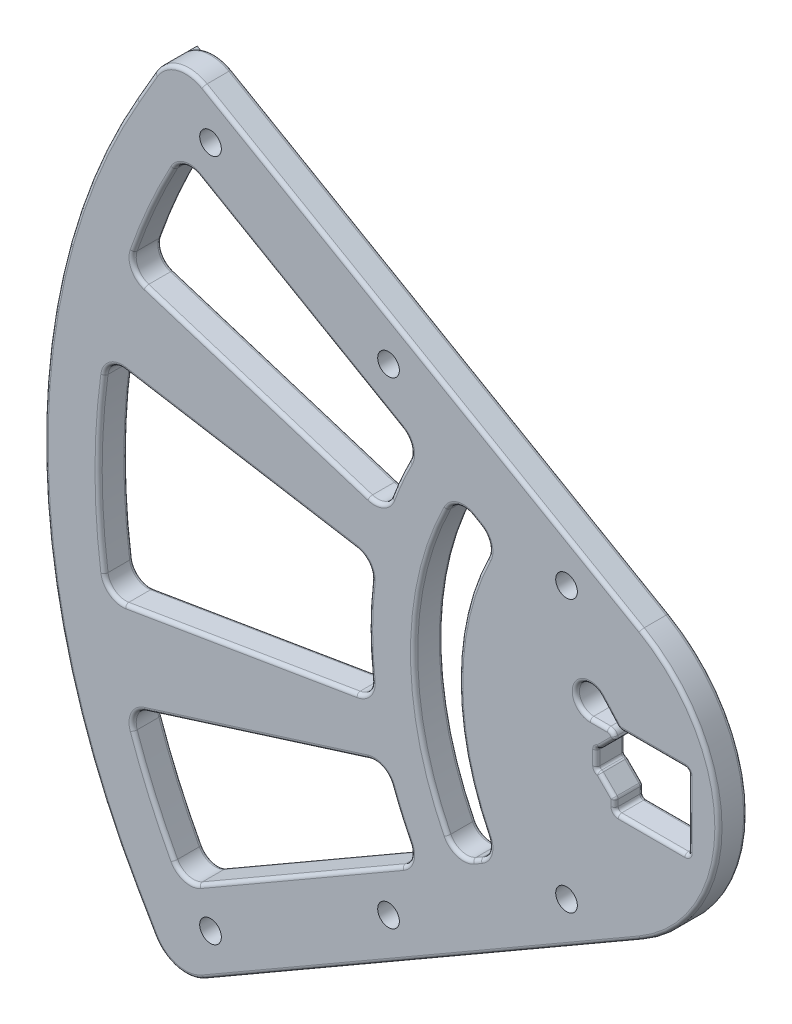
SolidWorks part; units mm, degrees
ref_plane "Front Plane" through (0, 0, 0) normal (0, 0, 1) x (1, 0, 0)
ref_plane "Top Plane" through (0, 0, 0) normal (0, 1, 0) x (1, 0, 0)
ref_plane "Right Plane" through (0, 0, 0) normal (1, 0, 0) x (0, 0, -1)
sketch "Sketch1" plane through (0, 0, 0) normal (0, 0, 1) x (1, 0, 0)
  line L0 (-3, 37.3205) -> (-366.7307, 247.3205) construction
  line L1 (-366.7307, -247.3205) -> (-3, -37.3205) construction
  line L2 (-66.0955, 46.0359) -> (-43.359, 32.909) construction
  line L3 (-66.9615, 46.5359) -> (-66.0955, 46.0359) construction
  line L4 (-66.9615, 46.5359) -> (-64.9615, 50) construction
  line L5 (-13, 20) -> (-376.7307, 230) construction
  line L6 (-43.359, -32.909) -> (-66.0955, -46.0359) construction
  line L7 (-66.0955, -46.0359) -> (-66.9615, -46.5359) construction
  line L8 (-64.9615, -50) -> (-66.9615, -46.5359) construction
  line L9 (-376.7307, -230) -> (-13, -20) construction
  line L10 (-10.25, 9.567) -> (-10.25, 2.75) construction
  line L11 (-2.75, 10.25) -> (-9.567, 10.25) construction
  line L12 (-2.75, 8) -> (-2.75, 10.25) construction
  line L13 (2, 7.25) -> (-2, 7.25) construction
  line L14 (2.75, 10.25) -> (2.75, 8) construction
  line L15 (9.567, 10.25) -> (2.75, 10.25) construction
  line L16 (10.25, 2.75) -> (10.25, 9.567) construction
  line L17 (8, 2.75) -> (10.25, 2.75) construction
  line L18 (7.25, -2) -> (7.25, 2) construction
  line L19 (10.25, -2.75) -> (8, -2.75) construction
  line L20 (10.25, -9.567) -> (10.25, -2.75) construction
  line L21 (2.75, -10.25) -> (9.567, -10.25) construction
  line L22 (2.75, -8) -> (2.75, -10.25) construction
  line L23 (-2, -7.25) -> (2, -7.25) construction
  line L24 (-2.75, -10.25) -> (-2.75, -8) construction
  line L25 (-9.567, -10.25) -> (-2.75, -10.25) construction
  line L26 (-10.25, -2.75) -> (-10.25, -9.567) construction
  line L27 (-8, -2.75) -> (-10.25, -2.75) construction
  line L28 (-7.25, 2) -> (-7.25, -2) construction
  line L29 (-10.25, 2.75) -> (-8, 2.75) construction
  line L30 (-30.3372, 25.3908) -> (-15.004, 16.5382) construction
  line L31 (-15.004, -16.5382) -> (-30.3372, -25.3908) construction
  line L32 (9, 10) -> (3.3, 10) construction
  line L33 (10, 3.3) -> (10, 9) construction
  line L34 (10, -9) -> (10, -3.3) construction
  line L35 (3.3, -10) -> (9, -10) construction
  line L36 (-3.3, 10) -> (-9, 10) construction
  line L37 (-10, 9) -> (-10, 3.3) construction
  line L38 (-10, -3.3) -> (-10, -9) construction
  line L39 (-9, -10) -> (-3.3, -10) construction
  line L40 (-3, -9.7) -> (-3, -8) construction
  line L41 (3, -8) -> (3, -9.7) construction
  line L42 (9.7, -3) -> (8, -3) construction
  line L43 (8, 3) -> (9.7, 3) construction
  line L44 (3, 9.7) -> (3, 8) construction
  line L45 (-3, 8) -> (-3, 9.7) construction
  line L46 (-9.7, 3) -> (-8, 3) construction
  line L47 (-8, 28.6603) -> (-371.7307, 238.6603) construction
  line L48 (-371.7307, -238.6603) -> (-8, -28.6603) construction
  line L49 (-2.7728, -18.7141) -> (-11, -23.4641) construction
  line L50 (3.2272, -29.1064) -> (-5, -33.8564) construction
  line L51 (3.2272, 29.1064) -> (-5, 33.8564) construction
  line L52 (-2.7728, 18.7141) -> (-11, 23.4641) construction
  line L53 (-3, 37.3205) -> (-366.7307, 247.3205)
  line L54 (-366.7307, -247.3205) -> (-3, -37.3205)
  line L55 (-66.0955, 46.0359) -> (-43.359, 32.909)
  line L56 (-66.9615, 46.5359) -> (-66.0955, 46.0359)
  line L57 (-66.9615, 46.5359) -> (-64.9615, 50)
  line L58 (-13, 20) -> (-376.7307, 230)
  line L59 (-43.359, -32.909) -> (-66.0955, -46.0359)
  line L60 (-66.0955, -46.0359) -> (-66.9615, -46.5359)
  line L61 (-64.9615, -50) -> (-66.9615, -46.5359)
  line L62 (-376.7307, -230) -> (-13, -20)
  line L63 (-10.25, 9.567) -> (-10.25, 2.75)
  line L64 (-2.75, 10.25) -> (-9.567, 10.25)
  line L65 (-2.75, 8) -> (-2.75, 10.25)
  line L66 (2, 7.25) -> (-2, 7.25)
  line L67 (2.75, 10.25) -> (2.75, 8)
  line L68 (9.567, 10.25) -> (2.75, 10.25)
  line L69 (10.25, 2.75) -> (10.25, 9.567)
  line L70 (8, 2.75) -> (10.25, 2.75)
  line L71 (7.25, -2) -> (7.25, 2)
  line L72 (10.25, -2.75) -> (8, -2.75)
  line L73 (10.25, -9.567) -> (10.25, -2.75)
  line L74 (2.75, -10.25) -> (9.567, -10.25)
  line L75 (2.75, -8) -> (2.75, -10.25)
  line L76 (-2, -7.25) -> (2, -7.25)
  line L77 (-2.75, -10.25) -> (-2.75, -8)
  line L78 (-9.567, -10.25) -> (-2.75, -10.25)
  line L79 (-10.25, -2.75) -> (-10.25, -9.567)
  line L80 (-8, -2.75) -> (-10.25, -2.75)
  line L81 (-7.25, 2) -> (-7.25, -2)
  line L82 (-10.25, 2.75) -> (-8, 2.75)
  line L83 (-30.3372, 25.3908) -> (-15.004, 16.5382)
  line L84 (-15.004, -16.5382) -> (-30.3372, -25.3908)
  line L85 (9, 10) -> (3.3, 10)
  line L86 (10, 3.3) -> (10, 9)
  line L87 (10, -9) -> (10, -3.3)
  line L88 (3.3, -10) -> (9, -10)
  line L89 (-3.3, 10) -> (-9, 10)
  line L90 (-10, 9) -> (-10, 3.3)
  line L91 (-10, -3.3) -> (-10, -9)
  line L92 (-9, -10) -> (-3.3, -10)
  line L93 (-3, -9.7) -> (-3, -8)
  line L94 (3, -8) -> (3, -9.7)
  line L95 (9.7, -3) -> (8, -3)
  line L96 (8, 3) -> (9.7, 3)
  line L97 (3, 9.7) -> (3, 8)
  line L98 (-3, 8) -> (-3, 9.7)
  line L99 (-9.7, 3) -> (-8, 3)
  line L100 (-8, 28.6603) -> (-371.7307, 238.6603)
  line L101 (-371.7307, -238.6603) -> (-8, -28.6603)
  line L102 (-2.7728, -18.7141) -> (-11, -23.4641)
  line L103 (3.2272, -29.1064) -> (-5, -33.8564)
  line L104 (3.2272, 29.1064) -> (-5, 33.8564)
  line L105 (-2.7728, 18.7141) -> (-11, 23.4641)
  arc A0 (-3, -37.3205) -> (-3, 37.3205) centre (-24.547, 0) ccw construction
  arc A1 (-41.209, 24.6342) -> (-41.209, -24.6342) centre (0, 0) ccw construction
  arc A2 (-41.209, 24.6342) -> (-43.359, 32.909) centre (-46.359, 27.7128) ccw construction
  arc A3 (-43.359, -32.909) -> (-41.209, -24.6342) centre (-46.359, -27.7128) ccw construction
  arc A4 (-9.567, 10.25) -> (-10.25, 9.567) centre (-10, 10) ccw construction
  arc A5 (-2.75, 8) -> (-2, 7.25) centre (-2, 8) ccw construction
  arc A6 (2, 7.25) -> (2.75, 8) centre (2, 8) ccw construction
  arc A7 (10.25, 9.567) -> (9.567, 10.25) centre (10, 10) ccw construction
  arc A8 (8, 2.75) -> (7.25, 2) centre (8, 2) ccw construction
  arc A9 (7.25, -2) -> (8, -2.75) centre (8, -2) ccw construction
  arc A10 (9.567, -10.25) -> (10.25, -9.567) centre (10, -10) ccw construction
  arc A11 (2.75, -8) -> (2, -7.25) centre (2, -8) ccw construction
  arc A12 (-2, -7.25) -> (-2.75, -8) centre (-2, -8) ccw construction
  arc A13 (-10.25, -9.567) -> (-9.567, -10.25) centre (-10, -10) ccw construction
  arc A14 (-8, -2.75) -> (-7.25, -2) centre (-8, -2) ccw construction
  arc A15 (-7.25, 2) -> (-8, 2.75) centre (-8, 2) ccw construction
  arc A16 (-13.1636, 11.9556) -> (-15.004, 16.5382) centre (-17.004, 13.0741) ccw construction
  arc A17 (-30.3372, 25.3908) -> (-37.0459, 23.7601) centre (-32.8372, 21.0607) ccw construction
  arc A18 (-37.0459, 23.7601) -> (-41.7472, 13.9325) centre (0, 0) ccw construction
  arc A19 (-41.7472, 13.9325) -> (-41.6942, 8.7139) centre (-34.1586, 11.3999) ccw construction
  arc A20 (-41.6942, -8.7139) -> (-41.6942, 8.7139) centre (-66.1408, 0) ccw construction
  arc A21 (-41.6942, -8.7139) -> (-41.7472, -13.9325) centre (-34.1586, -11.3999) ccw construction
  arc A22 (-41.7472, -13.9325) -> (-37.0459, -23.7601) centre (0, 0) ccw construction
  arc A23 (-37.0459, -23.7601) -> (-30.3372, -25.3908) centre (-32.8372, -21.0607) ccw construction
  arc A24 (-15.004, -16.5382) -> (-13.1636, -11.9556) centre (-17.004, -13.0741) ccw construction
  arc A25 (5.4234, -20.9103) -> (-2.7728, -18.7141) centre (0.2272, -23.9103) ccw construction
  arc A26 (3.2272, -29.1064) -> (5.4234, -20.9103) centre (0.2272, -23.9103) ccw construction
  arc A27 (5.4234, 20.9103) -> (3.2272, 29.1064) centre (0.2272, 23.9103) ccw construction
  arc A28 (-2.7728, 18.7141) -> (5.4234, 20.9103) centre (0.2272, 23.9103) ccw construction
  arc A29 (-3, -37.3205) -> (-3, 37.3205) centre (-24.547, 0) ccw
  arc A30 (-41.209, 24.6342) -> (-41.209, -24.6342) centre (0, 0) ccw
  arc A31 (-41.209, 24.6342) -> (-43.359, 32.909) centre (-46.359, 27.7128) ccw
  arc A32 (-43.359, -32.909) -> (-41.209, -24.6342) centre (-46.359, -27.7128) ccw
  arc A33 (-9.567, 10.25) -> (-10.25, 9.567) centre (-10, 10) ccw
  arc A34 (-2.75, 8) -> (-2, 7.25) centre (-2, 8) ccw
  arc A35 (2, 7.25) -> (2.75, 8) centre (2, 8) ccw
  arc A36 (10.25, 9.567) -> (9.567, 10.25) centre (10, 10) ccw
  arc A37 (8, 2.75) -> (7.25, 2) centre (8, 2) ccw
  arc A38 (7.25, -2) -> (8, -2.75) centre (8, -2) ccw
  arc A39 (9.567, -10.25) -> (10.25, -9.567) centre (10, -10) ccw
  arc A40 (2.75, -8) -> (2, -7.25) centre (2, -8) ccw
  arc A41 (-2, -7.25) -> (-2.75, -8) centre (-2, -8) ccw
  arc A42 (-10.25, -9.567) -> (-9.567, -10.25) centre (-10, -10) ccw
  arc A43 (-8, -2.75) -> (-7.25, -2) centre (-8, -2) ccw
  arc A44 (-7.25, 2) -> (-8, 2.75) centre (-8, 2) ccw
  arc A45 (-13.1636, 11.9556) -> (-15.004, 16.5382) centre (-17.004, 13.0741) ccw
  arc A46 (-30.3372, 25.3908) -> (-37.0459, 23.7601) centre (-32.8372, 21.0607) ccw
  arc A47 (-37.0459, 23.7601) -> (-41.7472, 13.9325) centre (0, 0) ccw
  arc A48 (-41.7472, 13.9325) -> (-41.6942, 8.7139) centre (-34.1586, 11.3999) ccw
  arc A49 (-41.6942, -8.7139) -> (-41.6942, 8.7139) centre (-66.1408, 0) ccw
  arc A50 (-41.6942, -8.7139) -> (-41.7472, -13.9325) centre (-34.1586, -11.3999) ccw
  arc A51 (-41.7472, -13.9325) -> (-37.0459, -23.7601) centre (0, 0) ccw
  arc A52 (-37.0459, -23.7601) -> (-30.3372, -25.3908) centre (-32.8372, -21.0607) ccw
  arc A53 (-15.004, -16.5382) -> (-13.1636, -11.9556) centre (-17.004, -13.0741) ccw
  arc A54 (5.4234, -20.9103) -> (-2.7728, -18.7141) centre (0.2272, -23.9103) ccw
  arc A55 (3.2272, -29.1064) -> (5.4234, -20.9103) centre (0.2272, -23.9103) ccw
  arc A56 (5.4234, 20.9103) -> (3.2272, 29.1064) centre (0.2272, 23.9103) ccw
  arc A57 (-2.7728, 18.7141) -> (5.4234, 20.9103) centre (0.2272, 23.9103) ccw
  circle A58 centre (-119.7502, 0) radius 150 construction
  ellipse E0 centre (-10.397, 0) end of major axis (-12.0389, 0) minor radius 1.625 construction
  ellipse E1 centre (-12.1609, 0) end of major axis (-12.1609, 1.625) minor radius 1.6082 construction
  ellipse E2 centre (-10.397, 0) end of major axis (-12.0389, 0) minor radius 1.625
  ellipse E3 centre (-12.1609, 0) end of major axis (-12.1609, 1.625) minor radius 1.6082
  spline S0 degree 3 poles (-1564.8389, -1269.6958) (138.9849, -43.531) (17.1493, -56.7892) (-15.7555, -8.3256) (-16.3488, -7.381) (-17.1461, -5.9011) (-17.3962, -5.3968) (-17.8512, -4.3591) (-18.0526, -3.833) (-18.388, -2.7622) (-18.5218, -2.2174) (-18.7042, -1.1042) (-18.7515, -0.5328) (-18.7484, 0.5892) (-18.6993, 1.1452) (-18.561, 1.9723) (-18.5041, 2.2469) (-18.3704, 2.794) (-18.2932, 3.0676) (-17.8664, 4.416) (-17.402, 5.4271) (-16.3485, 7.3806) (-15.7577, 8.3221) (15.0289, 53.6756) (131.2651, 55.4308) (-2012.6939, 16.2272) knots -6.318338 -6.318338 -6.318338 -6.318338 0.125 0.125 0.25 0.25 0.3125 0.3125 0.375 0.375 0.4375 0.4375 0.5 0.5 0.5625 0.5625 0.59375 0.59375 0.625 0.625 0.75 0.75 0.875 0.875 6.897704 6.897704 6.897704 6.897704 only from (-13.1636, -11.9556) to (-13.1636, 11.9556) construction
  spline S1 degree 3 poles (-13.1636, -11.9556) (-13.8432, -11.0696) (-14.5031, -10.1702) (-15.7555, -8.3256) (-16.3488, -7.381) (-17.1461, -5.9011) (-17.3962, -5.3968) (-17.8512, -4.3591) (-18.0526, -3.833) (-18.388, -2.7622) (-18.5218, -2.2174) (-18.7042, -1.1042) (-18.7515, -0.5328) (-18.7484, 0.5892) (-18.6993, 1.1452) (-18.561, 1.9723) (-18.5041, 2.2469) (-18.3704, 2.794) (-18.2932, 3.0676) (-17.8664, 4.416) (-17.402, 5.4271) (-16.3485, 7.3806) (-15.7577, 8.3221) (-14.5058, 10.1664) (-13.8427, 11.0702) (-13.1636, 11.9556) knots 0 0 0 0 0.125 0.125 0.25 0.25 0.3125 0.3125 0.375 0.375 0.4375 0.4375 0.5 0.5 0.5625 0.5625 0.59375 0.59375 0.625 0.625 0.75 0.75 0.875 0.875 1 1 1 1
  dimension "D1" = 300
sketch "Sketch3" plane through (0, 0, 0) normal (0, 0, 1) x (1, 0, 0)
  line L0 (-3, 37.3205) -> (-366.7307, 247.3205) construction
  line L1 (-366.7307, -247.3205) -> (-3, -37.3205) construction
  line L2 (-3, 37.3205) -> (-124.2436, 107.3205)
  line L3 (-124.2436, -107.3205) -> (-3, -37.3205)
  line L4 (-11.2881, 1.3649) -> (-11.2881, -1.3649) construction
  line L5 (-7.25, 2) -> (-7.25, -2) construction
  line L6 (-7.25, 2) -> (-7.25, -2) construction
  line L7 (2.75, -10.25) -> (9.567, -10.25) construction
  line L8 (10.25, -9.567) -> (10.25, -2.75) construction
  line L9 (9.567, 10.25) -> (2.75, 10.25) construction
  line L10 (-376.7307, -230) -> (-13, -20) construction
  line L11 (-15.3262, 2) -> (-15.3262, -2)
  line L12 (-171.2937, 0) -> (-141.8607, 0) construction
  line L13 (-137.9038, 103.6603) -> (-142.9038, 95)
  line L14 (-10.6066, 6.7177) -> (-14.3509, 2.9751)
  line L17 (-13, 20) -> (-376.7307, 230) construction
  line L18 (-10.25, -2.75) -> (-10.25, -9.567) construction
  line L19 (-10.25, -10.25) -> (10.25, -10.25)
  line L20 (-137.9038, -103.6603) -> (-142.9038, -95)
  line L21 (10.25, -10.25) -> (10.25, 10.25)
  line L22 (-64.9615, -50) -> (-66.9615, -46.5359) construction
  line L23 (-125.5196, 84.9632) -> (-69.1885, 52.4404)
  line L24 (-69.1885, -52.4404) -> (-125.5196, -84.9632)
  line L25 (-140.4207, 51.0979) -> (-78.3857, 31.5383)
  line L26 (-145.955, 28.046) -> (-81.8015, 17.3103)
  line L27 (-145.955, -28.046) -> (-81.8015, -17.3103)
  line L28 (-140.4207, -51.0979) -> (-78.3857, -31.5383)
  line L29 (10.25, 10.25) -> (-8.1842, 10.25)
  line L30 (-10.5431, -6.7812) -> (-14.3509, -2.9751)
  line L31 (-49.6747, 41.1742) -> (-47.5056, 39.9218)
  line L32 (-49.6747, -41.1742) -> (-47.5056, -39.9218)
  line L33 (-10.25, -7.4885) -> (-10.25, -10.25)
  line L34 (-14.0326, 15.752) -> (-9.6699, 10.9111)
  line L35 (-17.004, 9.0741) -> (-12.25, 9.0741)
  line L36 (-2.75, 10.25) -> (-9.567, 10.25) construction
  line L37 (-10.25, 9.0741) -> (-9.0741, 10.25) construction
  arc A0 (-3, -37.3205) -> (-3, 37.3205) centre (-24.547, 0) ccw construction
  arc A1 (-3, -37.3205) -> (-3, 37.3205) centre (-24.547, 0) ccw
  arc A2 (-7.25, 2) -> (-8, 2.75) centre (-8, 2) ccw construction
  arc A3 (-8, -2.75) -> (-7.25, -2) centre (-8, -2) ccw construction
  arc A4 (-7.25, 2) -> (-8, 2.75) centre (-8, 2) ccw construction
  arc A5 (-8, -2.75) -> (-7.25, -2) centre (-8, -2) ccw construction
  arc A6 (-14.7826, -2.721) -> (-15.3262, -2) centre (-14.5762, -2) cw
  arc A7 (-15.3262, 2) -> (-14.7826, 2.721) centre (-14.5762, 2) cw
  arc A8 (-13.1636, 11.9556) -> (-15.004, 16.5382) centre (-17.004, 13.0741) ccw construction
  arc A9 (-14.0326, 15.752) -> (-17.004, 9.0741) centre (-17.004, 13.0741) ccw
  arc A10 (-9.6699, 10.9111) -> (-8.1842, 10.25) centre (-8.1842, 12.25) ccw
  arc A11 (-12.25, 9.0741) -> (-10.3771, 7.7758) centre (-12.25, 7.0741) cw
  arc A12 (-142.9038, 95) -> (-142.9038, -95) centre (21.641, 0) ccw
  arc A13 (-132.4214, 83.0047) -> (-143.6395, 57.5096) centre (21.641, 0) ccw
  arc A14 (-67.2442, 45.8193) -> (-72.1906, 34.578) centre (21.641, 0) ccw
  arc A15 (-151.7338, 23.7944) -> (-151.7338, -23.7944) centre (21.641, 0) ccw
  arc A16 (-77.6616, 11.7894) -> (-77.6616, -11.7894) centre (21.641, 0) ccw
  arc A17 (-72.1906, -34.578) -> (-67.2442, -45.8193) centre (21.641, 0) ccw
  arc A18 (-143.6395, -57.5096) -> (-132.4214, -83.0047) centre (21.641, 0) ccw
  arc A19 (-49.6747, -41.1742) -> (-56.6484, -39.077) centre (-52.1747, -36.844) cw
  arc A20 (-47.5056, -39.9218) -> (-45.5277, -33.3672) centre (-50.0056, -35.5917) ccw
  arc A21 (-45.5277, 33.3672) -> (-47.5056, 39.9218) centre (-50.0056, 35.5917) ccw
  arc A22 (-56.6484, 39.077) -> (-49.6747, 41.1742) centre (-52.1747, 36.844) cw
  arc A23 (-67.2442, 45.8193) -> (-69.1885, 52.4404) centre (-71.6885, 48.1103) ccw
  arc A24 (-78.3857, 31.5383) -> (-72.1906, 34.578) centre (-76.8821, 36.3069) ccw
  arc A25 (-81.8015, -17.3103) -> (-77.6616, -11.7894) centre (-82.6267, -12.3789) ccw
  arc A26 (-81.8015, 17.3103) -> (-77.6616, 11.7894) centre (-82.6267, 12.3789) cw
  arc A27 (-78.3857, -31.5383) -> (-72.1906, -34.578) centre (-76.8821, -36.3069) cw
  arc A28 (-67.2442, -45.8193) -> (-69.1885, -52.4404) centre (-71.6885, -48.1103) cw
  arc A29 (-140.4207, -51.0979) -> (-143.6395, -57.5096) centre (-138.9172, -55.8665) ccw
  arc A30 (-132.4214, 83.0047) -> (-125.5196, 84.9632) centre (-128.0196, 80.6331) cw
  arc A31 (-56.6484, 39.077) -> (-56.6484, -39.077) centre (21.641, 0) ccw
  arc A32 (-45.5277, 33.3672) -> (-45.5277, -33.3672) centre (21.641, 0) ccw
  arc A33 (-140.4207, 51.0979) -> (-143.6395, 57.5096) centre (-138.9172, 55.8665) cw
  arc A34 (-145.955, 28.046) -> (-151.7338, 23.7944) centre (-146.7802, 23.1145) ccw
  arc A35 (-145.955, -28.046) -> (-151.7338, -23.7944) centre (-146.7802, -23.1145) cw
  arc A36 (-132.4214, -83.0047) -> (-125.5196, -84.9632) centre (-128.0196, -80.6331) ccw
  arc A37 (-137.9038, -103.6603) -> (-124.2436, -107.3205) centre (-129.2436, -98.6603) ccw
  arc A38 (-137.9038, 103.6603) -> (-124.2436, 107.3205) centre (-129.2436, 98.6603) cw
  arc A39 (-14.7826, 2.721) -> (-14.3509, 2.9751) centre (-15.0579, 3.6824) ccw
  arc A40 (-14.7826, -2.721) -> (-14.3509, -2.9751) centre (-15.0579, -3.6824) cw
  arc A41 (-10.5431, -6.7812) -> (-10.25, -7.4885) centre (-11.25, -7.4885) cw
  arc A42 (-10.6066, 6.7177) -> (-10.3771, 7.7758) centre (-11.3136, 7.4249) ccw
  ellipse E0 centre (-10.397, 0) end of major axis (-12.0389, 0) minor radius 1.625 construction
  ellipse E1 centre (-12.1609, 0) end of major axis (-12.1609, 1.625) minor radius 1.6082 construction
  point P92 (-54.1362, -43.75)
  point P95 (-43.3109, -37.5)
  point P98 (-43.3109, 37.5)
  point P101 (-54.1362, 43.75)
  point P104 (-64.9615, 50)
  point P107 (-73.7307, 30.0706)
  point P110 (-76.9875, -16.5048)
  point P113 (-76.9875, 16.5048)
  point P116 (-73.7307, -30.0706)
  point P119 (-64.9615, -50)
  point P122 (-145.2595, -52.6235)
  point P125 (-129.9134, 87.5)
  point P128 (-145.2595, 52.6235)
  point P131 (-150.959, 28.8833)
  point P134 (-150.959, -28.8833)
  point P137 (-129.9134, -87.5)
  point P139 (-132.9038, -112.3205)
  point P142 (-132.9038, 112.3205)
  point P145 (-14.5762, 2.75)
  point P148 (-14.5762, -2.75)
  point P151 (-10.25, -7.0741)
  point P154 (-10.25, 7.0741)
  dimension "D2" = 12.5
  dimension "D3" = 10
  dimension "D5" = 15
  dimension "D1" = 12.5
  dimension "D8" = 2
  dimension "D9" = 5
  dimension "D10" = 1
  dimension "D4" = 150
  dimension "D6" = 8
  dimension "D7" = 12.5
extrude "Boss-Extrude1" add sketch "Sketch3" along normal blind 8
sketch "Sketch6" plane through (0, 0, 8) normal (0, 0, 1) x (1, 0, 0)
  line L0 (-216.8485, 0) -> (-197.4652, 0) construction
  line L1 (-8, 28.6603) -> (-371.7307, 238.6603) construction
  line L3 (-122.3154, 94.6603) -> (-23.5885, 37.6603) construction
  line L4 (-137.9038, 103.6603) -> (-142.9038, 95) construction
  circle A0 centre (-122.3154, 94.6603) radius 1.6
  circle A1 centre (-23.5885, 37.6603) radius 1.6
  circle A2 centre (-122.3154, -94.6603) radius 1.6
  circle A3 centre (-23.5885, -37.6603) radius 1.6
  circle A4 centre (-72.9519, 66.1603) radius 1.6
  circle A5 centre (-72.9519, -66.1603) radius 1.6
  point P17 (-140.4038, 99.3301)
  dimension "D1" = 3.2
  dimension "D2" = 18
  dimension "D3" = 18
extrude "Cut-Extrude1" cut sketch "Sketch6" against normal through all
sketch "Sketch7" plane through (0, 0, 8) normal (0, 0, 1) x (1, 0, 0)
  circle A0 centre (-122.3154, 94.6603) radius 3
  circle A1 centre (-72.9519, 66.1603) radius 3
  circle A2 centre (-23.5885, 37.6603) radius 3
  circle A3 centre (-23.5885, -37.6603) radius 3
  circle A4 centre (-72.9519, -66.1603) radius 3
  circle A5 centre (-122.3154, -94.6603) radius 3
  dimension "D1" = 6
extrude "Cut-Extrude2" cut sketch "Sketch7" against normal offset from surface (6 mm away) 2 up to face at (-74.5519, -66.1603, 0)
sketch "Sketch8" plane through (0, 0, 0) normal (0, 0, -1) x (-1, 0, 0)
  line L0 (6.5, 31.2583) -> (136.0049, 106.028)
  line L1 (8, 28.6603) -> (371.7307, 238.6603) construction
  line L2 (8, 28.6603) -> (371.7307, 238.6603) construction
  line L3 (6.5, 31.2583) -> (8, 28.6603)
  line L4 (9.5, 26.0622) -> (8, 28.6603)
  line L5 (9.5, 26.0622) -> (139.0049, 100.8319)
  line L6 (139.0049, 100.8319) -> (139.4038, 101.0622)
  line L7 (137.9038, 103.6603) -> (142.9038, 95) construction
  line L8 (137.9038, 103.6603) -> (139.4038, 101.0622)
  line L9 (0, 0) -> (-65.3821, 0) construction
  line L10 (9.5, -26.0622) -> (8, -28.6603)
  line L11 (6.5, -31.2583) -> (8, -28.6603)
  line L12 (6.5, -31.2583) -> (136.0049, -106.028)
  line L13 (137.9038, -103.6603) -> (139.4038, -101.0622)
  line L14 (139.0049, -100.8319) -> (139.4038, -101.0622)
  line L15 (9.5, -26.0622) -> (139.0049, -100.8319)
  arc A0 (137.9038, 103.6603) -> (124.2436, 107.3205) centre (129.2436, 98.6603) ccw construction
  arc A1 (137.9038, 103.6603) -> (136.0049, 106.028) centre (129.2436, 98.6603) ccw
  circle A2 centre (23.5885, 37.6603) radius 1.6 construction
  circle A3 centre (72.9519, 66.1603) radius 1.6 construction
  circle A4 centre (122.3154, 94.6603) radius 1.6 construction
  circle A5 centre (23.5885, 37.6603) radius 1.6
  circle A6 centre (72.9519, 66.1603) radius 1.6
  circle A7 centre (122.3154, 94.6603) radius 1.6
  circle A8 centre (122.3154, -94.6603) radius 1.6
  circle A9 centre (72.9519, -66.1603) radius 1.6
  circle A10 centre (23.5885, -37.6603) radius 1.6
  arc A11 (137.9038, -103.6603) -> (136.0049, -106.028) centre (129.2436, -98.6603) cw
  dimension "D1" = 6
extrude "Boss-Extrude3" add sketch "Sketch8" along normal blind 2
fillet "Fillet3" radius 1 119 edges at (-143.3857, -53.6232, 8) (-138.5385, -70.4807, 8) (-129.3846, -85.4432, 8) (-97.3541, -68.7018, 8) (-66.8911, -49.5191, 8) (-69.8901, -40.2747, 8) (-74.6797, -31.8181, 8) (-109.4032, -41.3181, 8) (-78.6265, 15.3785, 8) (-113.8782, 22.6781, 8) (-149.7433, 27.142, 8) (-153.359, 0, 8) (-149.7433, -27.142, 8) (-113.8782, -22.6781, 8) (-78.6265, -15.3785, 8) (-78.359, 0, 8) (-129.3846, 85.4432, 8) (-138.5385, 70.4807, 8) (-143.3857, 53.6232, 8) (-109.4032, 41.3181, 8) (-74.6797, 31.8181, 8) (-69.8901, 40.2747, 8) (-66.8911, 49.5191, 8) (-97.3541, 68.7018, 8) (-45.2188, -37.0361, 8) (-53.359, 0, 8) (-45.2188, 37.0361, 8) (-48.5902, 40.548, 8) (-53.6147, 41.6322, 8) (-65.859, 0, 8) (-53.6147, -41.6322, 8) (-48.5902, -40.548, 8) (10.25, 0, 8) (1.0329, 10.25, 8) (-8.9973, 10.4227, 8) (-11.8513, 13.3315, 8) (-20.6586, 14.7002, 8) (-14.627, 9.0741, 8) (-11.1105, 8.7178, 8) (-10.3363, 7.213, 8) (-12.4788, 4.8464, 8) (-14.5506, 2.8206, 8) (-15.175, 2.4515, 8) (-15.3262, 0, 8) (-15.175, -2.4515, 8) (-14.5506, -2.8206, 8) (-12.447, -4.8782, 8) (-10.3262, -7.1057, 8) (-10.25, -8.8692, 8) (0, -10.25, 8) (-63.6218, -72.3205, 8) (-131.8317, -108.3195, 8) (-140.4038, -99.3301, 8) (-168.359, 0, 8) (-140.4038, 99.3301, 8) (-131.8317, 108.3195, 8) (-63.6218, 72.3205, 8) (18.547, 0, 8) (-74.6797, -31.8181, 0) (-109.4032, -41.3181, 0) (-143.3857, -53.6232, 0) (-138.5385, -70.4807, 0) (-129.3846, -85.4432, 0) (-97.3541, -68.7018, 0) (-66.8911, -49.5191, 0) (-69.8901, -40.2747, 0) (-78.6265, -15.3785, 0) (-78.359, 0, 0) (-78.6265, 15.3785, 0) (-113.8782, 22.6781, 0) (-149.7433, 27.142, 0) (-153.359, 0, 0) (-149.7433, -27.142, 0) (-113.8782, -22.6781, 0) (-66.8911, 49.5191, 0) (-97.3541, 68.7018, 0) (-129.3846, 85.4432, 0) (-138.5385, 70.4807, 0) (-143.3857, 53.6232, 0) (-109.4032, 41.3181, 0) (-74.6797, 31.8181, 0) (-69.8901, 40.2747, 0) (-53.6147, -41.6322, 0) (-48.5902, -40.548, 0) (-45.2188, -37.0361, 0) (-53.359, 0, 0) (-45.2188, 37.0361, 0) (-48.5902, 40.548, 0) (-53.6147, 41.6322, 0) (-65.859, 0, 0) (-10.25, -8.8692, 0) (0, -10.25, 0) (10.25, 0, 0) (1.0329, 10.25, 0) (-8.9973, 10.4227, 0) (-11.8513, 13.3315, 0) (-20.6586, 14.7002, 0) (-14.627, 9.0741, 0) (-11.1105, 8.7178, 0) (-10.3363, 7.213, 0) (-12.4788, 4.8464, 0) (-14.5506, 2.8206, 0) (-15.175, 2.4515, 0) (-15.3262, 0, 0) (-15.175, -2.4515, 0) (-14.5506, -2.8206, 0) (-12.447, -4.8782, 0) (-10.3262, -7.1057, 0) (10.25, 10.25, 4) (10.25, -10.25, 4) (-10.25, -10.25, 4) (18.547, 0, 0) (-63.6218, 72.3205, 0) (-130.3359, 108.6004, 0) (-141.1538, 98.0311, 0) (-168.359, 0, 0) (-141.1538, -98.0311, 0) (-130.3359, -108.6004, 0) (-63.6218, -72.3205, 0)
